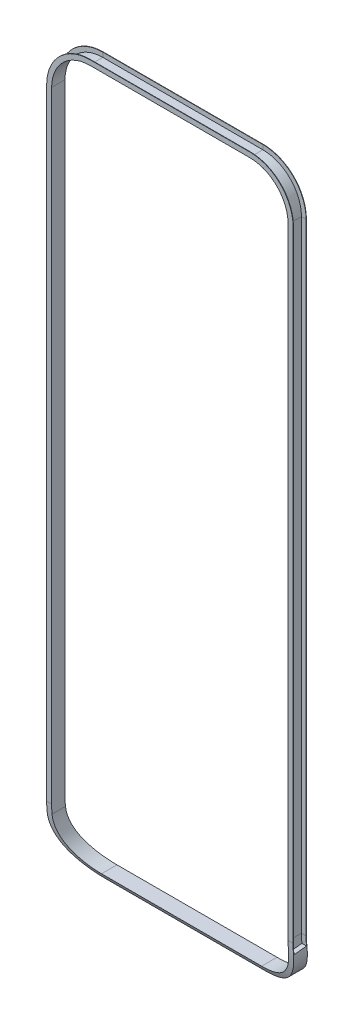
SolidWorks part; units mm, degrees
ref_plane "Front Plane" through (0, 0, 0) normal (0, 0, 1) x (1, 0, 0)
ref_plane "Top Plane" through (0, 0, 0) normal (0, 1, 0) x (1, 0, 0)
ref_plane "Right Plane" through (0, 0, 0) normal (1, 0, 0) x (0, 0, -1)
sketch "Sketch1" plane through (0, 0, 0) normal (0, 0, 1) x (1, 0, 0)
  line L0 (-13, 100) -> (-13, 1748)
  line L1 (100, 0) -> (519, 0)
  line L2 (0, 100) -> (0, 1748)
  line L3 (100, 1848) -> (519, 1848)
  line L4 (619, 100) -> (619, 1748)
  line L5 (100, 1861) -> (519, 1861)
  line L6 (632, 100) -> (632, 1748)
  line L7 (100, -13) -> (519, -13)
  arc A0 (100, 0) -> (0, 100) centre (100, 100) cw
  arc A1 (519, 0) -> (619, 100) centre (519, 100) ccw
  arc A2 (519, 1848) -> (619, 1748) centre (519, 1748) cw
  arc A3 (0, 1748) -> (100, 1848) centre (100, 1748) cw
  arc A4 (-13, 1748) -> (100, 1861) centre (100, 1748) cw
  arc A5 (519, 1861) -> (632, 1748) centre (519, 1748) cw
  arc A6 (519, -13) -> (632, 100) centre (519, 100) ccw
  arc A7 (100, -13) -> (-13, 100) centre (100, 100) cw
  point P8 (0, 0)
  point P11 (619, 0)
  point P14 (619, 1848)
  dimension "D3" = 100
  dimension "D1" = 1848
  dimension "D2" = 619
  dimension "D4" = 13
extrude "Boss-Extrude1" add sketch "Sketch1" against normal blind 100
sketch "Sketch2" plane through (0, 0, 0) normal (1, 0, 0) x (0, 0, -1)
  line L1 (0, 100) -> (0, -13) construction
  line L2 (35, 1861) -> (35, 123.5906)
  line L3 (100, -36.53) -> (53.9166, -36.53)
  line L7 (0, 123.5906) -> (0, -36.53)
  line L8 (0, -36.53) -> (53.9166, -36.53)
  line L9 (100, -36.53) -> (100, 1861)
  line L10 (100, 1861) -> (35, 1861)
  line L11 (100, 1861) -> (0, 1861) construction
  line L12 (100, 1748) -> (100, 1861) construction
  arc A0 (35, 123.5906) -> (100, -36.53) centre (264.72, 123.5906) ccw
  arc A1 (53.9166, -36.53) -> (0, 123.5906) centre (264.72, 123.5906) cw
  line M8 (0, 100) -> (100, 100)
  line M10 (100, 1748) -> (0, 1748)
  dimension "D2" = 264.72
  dimension "D1" = 35
  dimension "D3" = 23.53
extrude "Cut-Extrude1" cut sketch "Sketch2" along normal through all and the other way through all contours L8 A1 L7 M8 | A0 L9 M8 | L2 A0 M8 M10 | L9 L10 L2 A0 | A1 L7 L8 region at (0, 924.0729, -67.5029) region at (0, 48.817, -75.2659) region at (0, 2.3272, -15.8942)
ref_plane "Plane1" through (309.5, 0, 0) normal (1, 0, 0) x (0, 0, -1)
sketch "Sketch3" plane through (309.5, 0, 0) normal (1, 0, 0) x (0, 0, -1)
  line L0 (35, 1861) -> (0, 1861) construction
  line L1 (1, 1861) -> (34, 1861)
  line L2 (1, 1861) -> (1, 1849)
  line L3 (1, 1849) -> (34, 1849)
  line L4 (34, 1861) -> (34, 1849)
  line L5 (35, 1748) -> (35, 1861) construction
  line L6 (0, 1861) -> (0, 1748) construction
  dimension "D1" = 1
  dimension "D2" = 1
  dimension "D3" = 12
sketch3d "3DSketch1"
  line L0 (-13, 1748, -35) -> (-13, 123.5906, -35) construction
  line L2 (632, 1748, -35) -> (632, 123.5906, -35) construction
  line L3 (519, 1861, -35) -> (100, 1861, -35) construction
  line L4 (-13, 1748, -35) -> (-13, 123.5906, -35)
  line L6 (632, 1748, -35) -> (632, 123.5906, -35)
  line L7 (519, 1861, -35) -> (100, 1861, -35)
  arc A0 (100, 1861, -35) -> (-13, 1748, -35) centre (100, 1748, -35) ccw construction
  arc A1 (-13, 123.5906, -35) -> (-13, 100, -36.2145) centre (-13, 123.5906, -264.72) ccw construction
  arc A2 (632, 123.5906, -35) -> (632, 100, -36.2145) centre (632, 123.5906, -264.72) ccw construction
  arc A3 (632, 1748, -35) -> (519, 1861, -35) centre (519, 1748, -35) ccw construction
  arc A4 (100, 1861, -35) -> (-13, 1748, -35) centre (100, 1748, -35) ccw
  arc A5 (-13, 123.5906, -35) -> (-13, 100, -36.2145) centre (-13, 123.5906, -264.72) ccw
  arc A6 (632, 123.5906, -35) -> (632, 100, -36.2145) centre (632, 123.5906, -264.72) ccw
  arc A7 (632, 1748, -35) -> (519, 1861, -35) centre (519, 1748, -35) ccw
  point P3 (100, 1748, 78)
  point P4 (100, 1748, 78)
  point P7 (216.72, 123.5906, -264.72)
  point P9 (216.72, 123.5906, -264.72)
  point P10 (861.72, 123.5906, -264.72)
  point P12 (519, 1748, 78)
  point P19 (861.72, 123.5906, -264.72)
  point P25 (519, 1748, 78)
sweep "Cut-Sweep1" cut profiles "Sketch3" path "3DSketch1"
